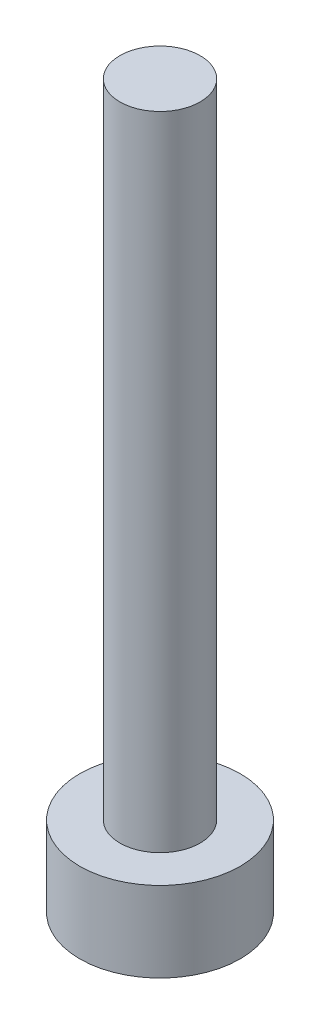
SolidWorks part; units mm, degrees
ref_plane "前视基准面" through (0, 0, 0) normal (0, 0, 1) x (1, 0, 0)
ref_plane "上视基准面" through (0, 0, 0) normal (0, 1, 0) x (1, 0, 0)
ref_plane "右视基准面" through (0, 0, 0) normal (1, 0, 0) x (0, 0, -1)
sketch "草图1" plane through (0, 0, 0) normal (0, 1, 0) x (1, 0, 0)
  circle A0 centre (0, 0) radius 2
  circle A1 centre (0, 0) radius 1
  dimension "D1" = 4
extrude "凸台-拉伸1" add sketch "草图1" against normal blind 2 contours A0 A1 | A1 region at (-1.9434, 0, 0) region at (0, 0, 0)
extrude "凸台-拉伸2" add sketch "草图1<3>" along normal blind 16 contours A1 region at (0, 0, 0)
sketch "草图1<3>" plane through (0, 0, 0) normal (0, 1, 0) x (1, 0, 0) same geometry as "草图1"
